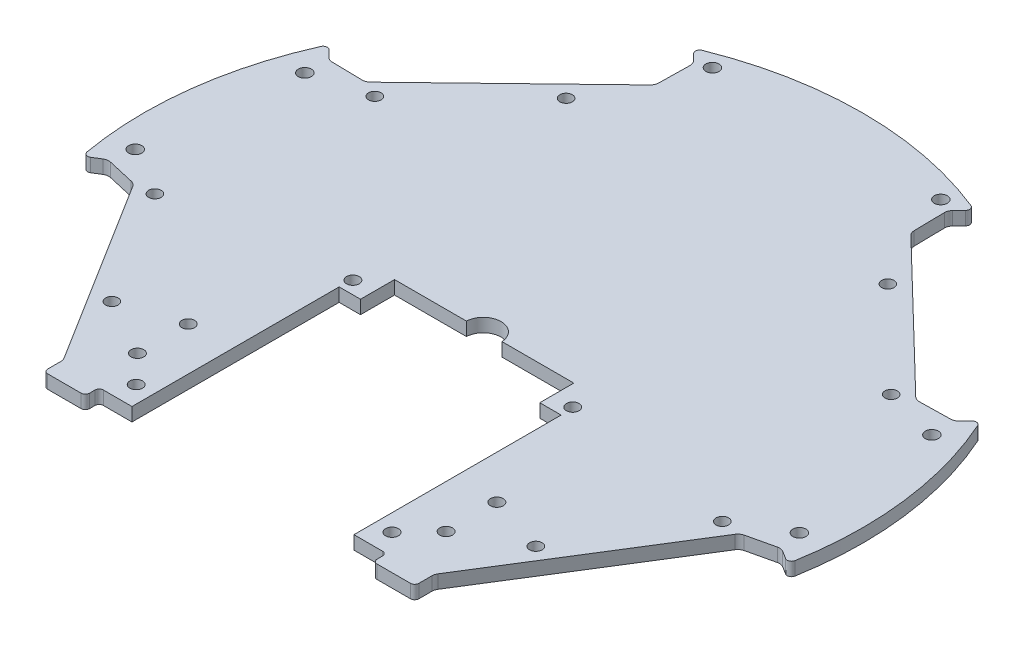
SolidWorks part; units mm, degrees
note: '?' marks a value the reader was unsure of.
material "6061 Alloy"
ref_plane "Front Plane" through (0, 0, 0) normal (0, 0, 1) x (1, 0, 0)
ref_plane "Top Plane" through (0, 0, 0) normal (0, 1, 0) x (1, 0, 0)
ref_plane "Right Plane" through (0, 0, 0) normal (1, 0, 0) x (0, 0, -1)
sketch "Sketch1" plane through (0, 0, 0) normal (0, 1, 0) x (1, 0, 0)
  line L0 (0, 0) -> (0, -62.55) construction
  line L1 (-83.4462, -16.178) -> (-71.2857, -8.5793) construction
  line L6 (0, 0) -> (-59.046, 61.1439) construction
  line L7 (0, 0) -> (-72.0841, -45.0431) construction
  line L8 (-33.174, 78.2591) -> (-23.2129, 67.9442) construction
  line L9 (-72.0841, -45.0431) -> (-70.388, -43.9833) construction
  line L10 (-70.388, -43.9833) -> (-84.9608, -20.662) construction
  line L11 (-84.9608, -20.662) -> (-72.2401, -12.7132) construction
  line L12 (-72.2401, -12.7132) -> (-43.0945, -59.3558) construction
  line L13 (-43.0945, -59.3558) -> (-55.8152, -67.3046) construction
  line L14 (-55.8152, -67.3046) -> (-70.388, -43.9833) construction
  line L21 (-59.046, 61.1439) -> (-57.6566, 59.7052)
  line L22 (-77.4385, 40.6021) -> (-37.8748, 78.8083) construction
  line L23 (-73.9694, 32.6911) -> (-77.0537, 35.885)
  line L24 (-37.8748, 78.8083) -> (-27.4549, 68.0182) construction
  line L25 (-27.4549, 68.0182) -> (-67.0186, 29.812) construction
  line L26 (-67.0186, 29.812) -> (-77.4385, 40.6021) construction
  line L27 (-43.0945, -64.8266) -> (-34, -64.8266)
  line L33 (-86.5505, -18.1178) -> (-71.2857, -8.5793) construction
  line L34 (0, 0) -> (0, 50000) construction
  line L35 (0, 0) -> (-50000, 0) construction
  line L36 (-57.5543, -62.55) -> (-19.8595, -62.55) construction
  line L38 (-67.0927, 25.57) -> (-79.5965, 38.5181) construction
  line L39 (-54.9774, -64.8266) -> (0, -64.8266) construction
  line L40 (-35.7168, 80.8923) -> (-23.2129, 67.9442) construction
  line L41 (-38.9606, -60.3102) -> (-54.2255, -69.8488) construction
  line L42 (-34, -62.55) -> (-19.8595, -62.55) construction
  line L43 (-43.0945, -64.8266) -> (-43.0945, -58.4123) construction
  line L45 (73.9694, 32.6911) -> (77.0537, 35.885)
  line L46 (-71.2857, -8.5793) -> (-38.9606, -60.3102) construction
  line L47 (83.4462, -16.178) -> (79.6809, -13.8252)
  line L48 (69.4846, -16.1792) -> (43.8945, -57.132)
  line L50 (43.0945, -64.8266) -> (34, -64.8266)
  line L51 (34, -62.55) -> (34, -64.8266)
  line L52 (0, 0) -> (72.0841, -45.0431) construction
  line L53 (0, 0) -> (59.046, 61.1439) construction
  line L54 (-30.0897, 75.0653) -> (-30.2847, 63.8954)
  line L55 (-62.7996, 32.4961) -> (-30.2847, 63.8954)
  line L56 (-30.0897, 75.0653) -> (-33.174, 78.2591)
  line L57 (73.9694, 32.6911) -> (77.0537, 35.885)
  line L58 (30.0897, 75.0653) -> (33.174, 78.2591)
  line L59 (-34, -62.55) -> (-34, -61.55)
  line L60 (62.7996, 32.4961) -> (30.2847, 63.8954)
  line L61 (-73.9694, 32.6911) -> (-62.7996, 32.4961)
  line L62 (-77.0537, 35.885) -> (-67.0927, 25.57) construction
  line L63 (-83.4462, -16.178) -> (-79.6809, -13.8252)
  line L64 (-79.6809, -13.8252) -> (-69.4846, -16.1792)
  line L65 (-69.4846, -16.1792) -> (-43.8945, -57.132)
  line L66 (-27.4549, 68.0182) -> (-23.2129, 67.9442) construction
  line L67 (-72.2401, -12.7132) -> (-71.2857, -8.5793) construction
  line L68 (30.0897, 75.0653) -> (30.2847, 63.8954)
  line L69 (73.9694, 32.6911) -> (62.7996, 32.4961)
  line L70 (-34, -62.55) -> (-34, -64.8266)
  line L71 (79.6809, -13.8252) -> (69.4846, -16.1792)
  line L72 (-34, -61.55) -> (-20, -61.55)
  line L73 (-20, -61.55) -> (-19.8595, -62.55)
  line L74 (-19.8595, -62.55) -> (19.8595, -62.55)
  line L75 (20, -61.55) -> (19.8595, -62.55)
  line L76 (34, -61.55) -> (20, -61.55)
  line L77 (34, -62.55) -> (34, -61.55)
  line L78 (-43.0945, -64.8266) -> (-43.8945, -64.8266)
  line L79 (-19.8595, -62.55) -> (0, -62.55) construction
  line L80 (-19.8595, -62.55) -> (34, -62.55) construction
  line L81 (-43.8945, -64.8266) -> (-43.8945, -57.132)
  line L82 (-43.0945, -58.4123) -> (-43.8945, -57.132) construction
  line L83 (43.8945, -64.8266) -> (43.8945, -57.132)
  line L84 (43.0945, -64.8266) -> (43.8945, -64.8266)
  line L97 (-23.2129, 67.9442) -> (-67.0927, 25.57) construction
  circle A0 centre (0, 0) radius 85 construction
  circle A1 centre (0, 0) radius 90 construction
  arc A51 (-77.0537, 35.885) -> (-83.4462, -16.178) centre (0, 0) ccw
  arc A52 (77.0537, 35.885) -> (83.4462, -16.178) centre (0, 0) cw
  arc A54 (-33.174, 78.2591) -> (33.174, 78.2591) centre (0, 0) cw
  point P29 (-31.6318, 76.6622)
  point P33 (-47.2368, 48.9151)
  point P34 (31.6318, 76.6622)
  point P35 (-57.6673, -36.0345)
  point P85 (-57.6566, 59.7052)
  dimension "D2" = 58
  dimension "D10" = 82
  dimension "D12" = 170
  dimension "D14" = 34
  dimension "D13" = 1
  dimension "D15" = 3
  dimension "D3" = 180
  dimension "D4" = 64.8266
  dimension "D5" = 44
  dimension "D6" = 15
  dimension "D7" = 55
  dimension "D8" = 62.55
  dimension "D9" = 2
  dimension "D11" = 2
  dimension "D16" = 7
  dimension "D17" = 7
  dimension "D18" = 0.5
  dimension "D19" = 1
  dimension "D20" = 14
  dimension "D21" = 0.8
extrude "Boss-Extrude4" add sketch "Sketch1" along normal mid plane 3.175
ref_point "Rear_Axle_Center (L)"
ref_axis "Rear_Axle_Proj (L)" through (46.5421, 0, -48.1958) along (0, 1, 0)?
ref_point "Front_Axle_Center (L)"
ref_axis "Front_Axle_Proj (L)" through (57.2432, 0, 35.7696) along (0, 1, 0)?
ref_point "Front_Axle_Center (R)"
ref_axis "Front_Axle_Proj (R)" through (-57.2432, 0, 35.7696) along (0, 1, 0)?
ref_point "Read_Axle_Center (R)"
ref_axis "Rear_Axle_Proj (R)" through (-46.5421, 0, -48.1958) along (0, 1, 0)?
sketch "Sketch17" plane through (0, 1.5875, 0) normal (0, 1, 0) x (1, 0, 0)
  line L0 (0, -57.55) -> (0, -62.55) construction
  line L1 (-19.8595, -62.55) -> (19.8595, -62.55) construction
  circle A0 centre (0, -57.55) radius 8.5
  dimension "D1" = 17
  dimension "D2" = 5
extrude "Boss-Extrude5" [suppressed] add sketch "Sketch17" against normal up to surface (3.175 mm away)
ref_plane "Plane1" through (0, 0, 10) normal (0, 0, 1) x (1, 0, 0)
hole_wizard "M3 Clearance Hole3" positions "Sketch18" profile "Sketch19" hole size "M3" standard "ANSI Metric" end condition through all
sketch "Sketch18" plane through (0, -1.5875, 0) normal (0, -1, 0) x (-1, 0, 0)
  line L0 (-36.5, -50) -> (-36.5, -38) construction
  line L3 (0, 0) -> (0, -38) construction
  line L4 (36.5, -50) -> (36.5, -38) construction
  line L6 (0, -38) -> (36.5, -38) construction
  line L8 (0, -38) -> (-36.5, -38) construction
  line L9 (-36.5, -44) -> (36.5, -44) construction
  line L10 (0, -44) -> (0, 0) construction
  point P1 (36.5, -50)
  point P3 (36.5, -38)
  point P5 (-36.5, -50)
  point P33 (-36.5, -38)
  dimension "D1" = 12
  dimension "D2" = 73
  dimension "D4" = 38
sketch "Sketch19" plane through (-36.5, -1.5875, 50) normal (1, 0, 0) x (0, 0, -1)
  line L0 (0, 0) -> (0, 3.175)
  line L1 (0, 3.175) -> (1.5, 3.175)
  line L2 (1.5, 3.175) -> (1.5, 0)
  line L5 (1.5, 0) -> (0, 0)
  line L11 (0, -6.35) -> (0, 107.95) construction
  dimension "Thru Hole Dia." = 3
  dimension "Thru Hole Depth" = 3.175
hole_wizard "M3 Clearance Hole1" positions "Sketch11" profile "Sketch12" hole size "M3" standard "ANSI Metric" end condition through all
sketch "Sketch11" plane through (0, 1.5875, 0) normal (0, 1, 0) x (1, 0, 0)
  line L0 (83.4462, -16.178) -> (79.6809, -13.8252) construction
  line L2 (73.9694, 32.6911) -> (77.0537, 35.885) construction
  line L4 (-73.9694, 32.6911) -> (-77.0537, 35.885) construction
  line L6 (0, 0) -> (0, -50000) construction
  line L7 (78.4111, 9.6277) -> (84.3664, 10.3589) construction
  line L10 (74.155, 27.2403) -> (78.5423, -8.4914) construction
  line L12 (78.4111, 9.6277) -> (76.3487, 9.3744) construction
  arc A7 (77.964, -12.7523) -> (72.563, 31.2347) centre (0, 0) ccw construction
  arc A13 (-77.964, -12.7523) -> (-72.563, 31.2347) centre (0, 0) cw construction
  arc A17 (83.4462, -16.178) -> (77.0537, 35.885) centre (0, 0) ccw construction
  point P34 (78.5423, -8.4914)
  point P66 (74.155, 27.2403)
  point P70 (-74.155, 27.2403)
  point P71 (-78.5423, -8.4914)
  dimension "D1" = 6
  dimension "D2" = 36
sketch "Sketch12" plane through (-78.5423, 1.5875, 8.4914) normal (1, 0, 0) x (0, 0, 1)
  line L0 (0, 0) -> (0, 3.175)
  line L1 (0, 3.175) -> (1.55, 3.175)
  line L2 (1.55, 3.175) -> (1.55, 0)
  line L5 (1.55, 0) -> (0, 0)
  line L11 (0, -6.35) -> (0, 107.95) construction
  dimension "Thru Hole Dia." = 3.1
  dimension "Thru Hole Depth" = 3.175
hole_wizard "M3 Clearance Hole4" positions "Sketch9" profile "Sketch10" hole size "M3" standard "ANSI Metric" end condition through all
sketch "Sketch9" plane through (0, -1.5875, 0) normal (0, -1, 0) x (-1, 0, 0)
  line L0 (0, 0) -> (0, 63.4318) construction
  line L1 (-38.0437, 52.9272) -> (38.0437, 52.9272) construction
  line L3 (61.0625, 30.6981) -> (-61.0625, 30.6981) construction
  line L4 (-67.0993, -15.2789) -> (67.0993, -15.2789) construction
  line L5 (50.1419, -42.4164) -> (-50.1419, -42.4164) construction
  line L6 (-61.0625, 30.6981) -> (-38.0437, 52.9272) construction
  line L7 (38.0437, 52.9272) -> (61.0625, 30.6981) construction
  line L8 (67.0993, -15.2789) -> (50.1419, -42.4164) construction
  line L9 (-50.1419, -42.4164) -> (-67.0993, -15.2789) construction
  line L10 (0, 0) -> (-44.8055, 46.3974) construction
  line L11 (0, 0) -> (44.8055, 46.3974) construction
  line L12 (0, 0) -> (-96.9468, 0) construction
  line L14 (-55.1231, -34.4448) -> (0, 0) construction
  line L15 (0, 0) -> (55.1231, -34.4448) construction
  line L18 (-69.4846, -16.1792) -> (-43.8945, -57.132) construction
  line L19 (-62.7996, 32.4961) -> (-30.2847, 63.8954) construction
  point P0 (-67.0993, -15.2789)
  point P2 (-50.1419, -42.4164)
  point P9 (-61.0625, 30.6981)
  point P11 (-38.0437, 52.9272)
  point P30 (50.1419, -42.4164)
  point P31 (67.0993, -15.2789)
  point P32 (38.0437, 52.9272)
  point P33 (61.0625, 30.6981)
  dimension "D9" = 46
  dimension "D10" = 46
  dimension "D11" = 32
  dimension "D12" = 32
  dimension "D7" = 58
  dimension "D5" = 32
  dimension "D6" = 2.5
  dimension "D8" = 9.4
  dimension "D2" = 44
  dimension "D3" = 32
  dimension "D4" = 2.5
  dimension "D13" = 9.4
sketch "Sketch10" plane through (67.0993, -1.5875, 15.2789) normal (1, 0, 0) x (0, 0, -1)
  line L0 (0, 0) -> (0, 3.175)
  line L1 (0, 3.175) -> (1.475, 3.175)
  line L2 (1.475, 3.175) -> (1.475, 0)
  line L5 (1.475, 0) -> (0, 0)
  line L11 (0, -6.35) -> (0, 107.95) construction
  dimension "Thru Hole Dia." = 2.95
  dimension "Thru Hole Depth" = 3.175
hole_wizard "M3 Clearance Hole2" positions "Sketch13" profile "Sketch14" hole size "M3" standard "ANSI Metric" end condition through all
sketch "Sketch13" plane through (0, 1.5875, 0) normal (0, 1, 0) x (1, 0, 0)
  line L0 (0, 0) -> (0, 85) construction
  line L2 (-24, 47) -> (-24, 81) construction
  line L3 (-24, 47) -> (24, 47) construction
  line L4 (-24, 81) -> (24, 81) construction
  line L5 (24, 47) -> (24, 81) construction
  line L6 (-24, 47) -> (24, 81) construction
  line L7 (-24, 81) -> (24, 47) construction
  line L8 (-38.0437, 52.9272) -> (-61.0625, 30.6981) construction
  line L10 (-36.307, 51.1289) -> (-59.3259, 28.8998) construction
  line L11 (-16.3488, 39.8187) -> (-31.6313, 55.6441) construction
  line L12 (-16.3488, 39.8187) -> (-48.7191, 8.559) construction
  line L13 (-31.6313, 55.6441) -> (-64.0016, 24.3845) construction
  line L14 (-48.7191, 8.559) -> (-64.0016, 24.3845) construction
  line L15 (-16.3488, 39.8187) -> (-64.0016, 24.3845) construction
  line L16 (-31.6313, 55.6441) -> (-48.7191, 8.559) construction
  line L17 (-49.5531, 41.8127) -> (-40.1752, 32.1016) construction
  line L18 (-27, 76.4978) -> (-27, 80.5978) construction
  arc A0 (33.174, 78.2591) -> (-33.174, 78.2591) centre (0, 0) ccw construction
  circle A1 centre (-16.2162, 44) radius 3 construction
  circle A2 centre (-27, 76.4978) radius 3 construction
  point P65 (0, 64)
  point P181 (-27, 76.4978)
  point P184 (27, 76.4978)
  dimension "D7" = 6
  dimension "D1" = 48
  dimension "D2" = 34
  dimension "D3" = 4
  dimension "D5" = 45
  dimension "D6" = 22
  dimension "D8" = 4.1
  dimension "D4" = 2.5
sketch "Sketch14" plane through (27, 1.5875, -76.4978) normal (1, 0, 0) x (0, 0, 1)
  line L0 (0, 0) -> (0, 3.175)
  line L1 (0, 3.175) -> (1.55, 3.175)
  line L2 (1.55, 3.175) -> (1.55, 0)
  line L5 (1.55, 0) -> (0, 0)
  line L11 (0, -6.35) -> (0, 107.95) construction
  dimension "Thru Hole Dia." = 3.1
  dimension "Thru Hole Depth" = 3.175
hole_wizard "M3 Clearance Hole5" [suppressed] positions "Sketch24" profile "Sketch25" hole size "M3" standard "ANSI Metric"
sketch "Sketch24" plane through (0, 1.5875, 0) normal (0, 1, 0) x (1, 0, 0)
  line L1 (-11, -4.4) -> (11, -4.4) construction
  line L2 (11, -4.4) -> (11, -36.4) construction
  line L3 (11, -36.4) -> (-11, -36.4) construction
  line L4 (-11, -36.4) -> (-11, -4.4) construction
  line L7 (-11, 37.6) -> (11, 37.6) construction
  line L8 (0, -4.4) -> (0, 0) construction
  line L9 (0, 0) -> (0, 37.6) construction
  point P8 (-11, -4.4)
  point P10 (11, -4.4)
  point P12 (11, -36.4)
  point P14 (-11, -36.4)
  point P42 (-11, 37.6)
  point P45 (11, 37.6)
  dimension "D1" = 22
  dimension "D2" = 32
  dimension "D3" = 4.4
  dimension "D4" = 42
sketch "Sketch25" plane through (-11, 1.5875, 4.4) normal (1, 0, 0) x (0, 0, 1)
  line L0 (0, 0) -> (0, 3.175)
  line L1 (0, 3.175) -> (1.5, 3.175)
  line L2 (1.5, 3.175) -> (1.5, 0)
  line L5 (1.5, 0) -> (0, 0)
  line L11 (0, -6.35) -> (0, 107.95) construction
  dimension "Thru Hole Dia." = 3
  dimension "Thru Hole Depth" = 3.175
sketch "Sketch20" plane through (0, 1.5875, 0) normal (0, 1, 0) x (1, 0, 0)
  line L0 (-16.1485, 44) -> (-16.1485, 39) construction
  line L1 (-14.6485, 44) -> (-14.6485, 39)
  line L2 (-17.6485, 44) -> (-17.6485, 39)
  line L3 (0, 0) -> (0, 85) construction
  line L5 (16.1485, 44) -> (16.1485, 39) construction
  line L6 (14.6485, 44) -> (14.6485, 39)
  line L7 (17.6485, 44) -> (17.6485, 39)
  arc A0 (-14.6485, 44) -> (-17.6485, 44) centre (-16.1485, 44) ccw
  arc A1 (-17.6485, 39) -> (-14.6485, 39) centre (-16.1485, 39) ccw
  arc A5 (33.174, 78.2591) -> (-33.174, 78.2591) centre (0, 0) ccw construction
  arc A7 (14.6485, 44) -> (17.6485, 44) centre (16.1485, 44) cw
  arc A8 (17.6485, 39) -> (14.6485, 39) centre (16.1485, 39) cw
  point P2 (-16.1485, 41.5)
  point P16 (16.1485, 41.5)
  dimension "D1" = 44
  dimension "D2" = 3
  dimension "D3" = 5
  dimension "D4" = 16.1485
extrude "Cut-Extrude1" [suppressed] cut sketch "Sketch20" against normal through all
sketch "Sketch22" plane through (0, 1.5875, 0) normal (0, 1, 0) x (1, 0, 0)
  line L0 (-56.6896, -36.6556) -> (-58.0464, -37.5035) construction
  line L1 (-69.4846, -16.1792) -> (-43.8945, -57.132) construction
  line L3 (30.2452, 66.1578) -> (65.062, 32.5356)
  line L4 (71.6894, -15.6702) -> (43.8945, -60.1514)
  line L5 (-19.8595, -62.55) -> (19.8595, -62.55) construction
  line L6 (-43.8945, -64.8266) -> (-43.8945, -57.132) construction
  line L28 (-30.2452, 66.1578) -> (-65.062, 32.5356)
  line L29 (-71.6894, -15.6702) -> (-43.8945, -60.1514)
  line L30 (-79.6809, -13.8252) -> (-69.4846, -16.1792) construction
  line L31 (0, 85) -> (0, -62.55) construction
  line L32 (-46.5421, 48.1958) -> (-47.6536, 49.3467) construction
  line L37 (-20, -61.55) -> (-19.8595, -62.55)
  line L38 (-20, -61.55) -> (-19.8595, -62.55)
  line L40 (-43.8945, -57.132) -> (-43.8945, -64.8266)
  line L41 (-43.8945, -57.132) -> (-43.8945, -64.8266)
  line L43 (43.8945, -64.8266) -> (43.8945, -57.132)
  line L44 (43.8945, -64.8266) -> (43.8945, -57.132)
  line L56 (-19.8595, -62.55) -> (19.8595, -62.55)
  line L58 (19.8595, -62.55) -> (20, -61.55)
  line L59 (20, -61.55) -> (34, -61.55)
  line L60 (34, -61.55) -> (34, -64.8266)
  line L61 (34, -64.8266) -> (43.8945, -64.8266)
  line L63 (43.8945, -57.132) -> (69.4846, -16.1792)
  line L64 (69.4846, -16.1792) -> (79.6809, -13.8252)
  line L65 (79.6809, -13.8252) -> (83.4462, -16.178)
  line L66 (77.0537, 35.885) -> (73.9694, 32.6911)
  line L67 (73.9694, 32.6911) -> (62.7996, 32.4961)
  line L68 (62.7996, 32.4961) -> (30.2847, 63.8954)
  line L69 (30.2847, 63.8954) -> (30.0897, 75.0653)
  line L70 (30.0897, 75.0653) -> (33.174, 78.2591)
  line L71 (-33.174, 78.2591) -> (-30.0897, 75.0653)
  line L72 (-30.0897, 75.0653) -> (-30.2847, 63.8954)
  line L73 (-30.2847, 63.8954) -> (-62.7996, 32.4961)
  line L74 (-62.7996, 32.4961) -> (-73.9694, 32.6911)
  line L75 (-73.9694, 32.6911) -> (-77.0537, 35.885)
  line L76 (-83.4462, -16.178) -> (-79.6809, -13.8252)
  line L77 (-79.6809, -13.8252) -> (-69.4846, -16.1792)
  line L78 (-69.4846, -16.1792) -> (-43.8945, -57.132)
  line L80 (-43.8945, -64.8266) -> (-34, -64.8266)
  line L81 (-34, -64.8266) -> (-34, -61.55)
  line L82 (-34, -61.55) -> (-20, -61.55)
  line L84 (-19.8595, -62.55) -> (19.8595, -62.55)
  line L86 (19.8595, -62.55) -> (20, -61.55)
  line L87 (20, -61.55) -> (34, -61.55)
  line L88 (34, -61.55) -> (34, -64.8266)
  line L89 (34, -64.8266) -> (43.8945, -64.8266)
  line L91 (43.8945, -57.132) -> (69.4846, -16.1792)
  line L92 (69.4846, -16.1792) -> (79.6809, -13.8252)
  line L93 (79.6809, -13.8252) -> (83.4462, -16.178)
  line L94 (77.0537, 35.885) -> (73.9694, 32.6911)
  line L95 (73.9694, 32.6911) -> (62.7996, 32.4961)
  line L96 (62.7996, 32.4961) -> (30.2847, 63.8954)
  line L97 (30.2847, 63.8954) -> (30.0897, 75.0653)
  line L98 (30.0897, 75.0653) -> (33.174, 78.2591)
  line L99 (-33.174, 78.2591) -> (-30.0897, 75.0653)
  line L100 (-30.0897, 75.0653) -> (-30.2847, 63.8954)
  line L101 (-30.2847, 63.8954) -> (-62.7996, 32.4961)
  line L102 (-62.7996, 32.4961) -> (-73.9694, 32.6911)
  line L103 (-73.9694, 32.6911) -> (-77.0537, 35.885)
  line L104 (-83.4462, -16.178) -> (-79.6809, -13.8252)
  line L105 (-79.6809, -13.8252) -> (-69.4846, -16.1792)
  line L106 (-69.4846, -16.1792) -> (-43.8945, -57.132)
  line L108 (-43.8945, -64.8266) -> (-34, -64.8266)
  line L109 (-34, -64.8266) -> (-34, -61.55)
  line L110 (-34, -61.55) -> (-20, -61.55)
  arc A9 (83.4462, -16.178) -> (77.0537, 35.885) centre (0, 0) ccw
  arc A10 (33.174, 78.2591) -> (-33.174, 78.2591) centre (0, 0) ccw
  arc A11 (-77.0537, 35.885) -> (-83.4462, -16.178) centre (0, 0) ccw
  arc A13 (83.4462, -16.178) -> (77.0537, 35.885) centre (0, 0) ccw
  arc A14 (33.174, 78.2591) -> (-33.174, 78.2591) centre (0, 0) ccw
  arc A15 (-77.0537, 35.885) -> (-83.4462, -16.178) centre (0, 0) ccw
  dimension "D2" = 1.6
  dimension "D1" = 0
extrude "Boss-Extrude6" add sketch "Sketch22" against normal up to surface (3.175 mm away) up to face at (-27, -1.5875, -74.9478)
fillet "Fillet1" radius 2 14 edges at (-30.0897, 0, -75.0653) (30.0897, 0, -75.0653) (-79.6809, 0, 13.8252) (79.6809, 0, 13.8252) (73.9694, 0, -32.6911) (-73.9694, 0, -32.6911) (65.062, 0, -32.5356) (30.2452, 0, -66.1578) (71.6894, 0, 15.6702) (-71.6894, 0, 15.6702) (-65.062, 0, -32.5356) (-30.2452, 0, -66.1578) (43.8945, 0, 60.1514) (-43.8945, 0, 60.1514)
fillet "Fillet3" radius 1 12 edges at (-77.0537, 0, -35.885) (77.0537, 0, -35.885) (83.4462, 0, 16.178) (34, 0, 64.8266) (-34, 0, 64.8266) (-33.174, 0, -78.2591) (33.174, 0, -78.2591) (-83.4462, 0, 16.178) (34, 0, 61.55) (-34, 0, 61.55) (-43.8945, 0, 64.8266) (43.8945, 0, 64.8266)
sketch "Sketch23" [suppressed] plane through (0, 3.175, 0) normal (0, 1, 0) x (1, 0, 0)
  circle A0 centre (0, -53.55) radius 4.95
  dimension "D1" = 9.9
fillet "Fillet6" radius 0.5 4 edges at (20, 0, 61.55) (19.8595, 0, 62.55) (-20, 0, 61.55) (-19.8595, 0, 62.55)
sketch "Sketch28" plane through (0, 1.5875, 0) normal (0, 1, 0) x (1, 0, 0)
  line L0 (-19.4248, -62.55) -> (19.4248, -62.55) construction
  line L1 (-19.4248, -62.55) -> (19.4248, -62.55) construction
  line L2 (-26.25, -62.55) -> (26.25, -62.55)
  line L3 (-26.25, -62.55) -> (-26.25, -12.55)
  line L4 (26.25, -62.55) -> (26.25, -12.55)
  line L5 (-26.25, -12.55) -> (26.25, -12.55)
  line L6 (0, -4.7) -> (0, -77.8833) construction
  line L7 (-21, -4.7) -> (-21, -12.55) construction
  line L8 (21, -4.7) -> (4, -4.7) construction
  line L9 (21, -4.7) -> (21, -12.55) construction
  line L10 (-4, -4.7) -> (-21, -4.7) construction
  line L11 (21.2, -4.5) -> (21.2, -12.55)
  line L12 (21.2, -4.5) -> (4.1952, -4.5)
  line L13 (-4.1952, -4.5) -> (-21.2, -4.5)
  line L14 (-21.2, -4.5) -> (-21.2, -12.55)
  arc A0 (19.4248, -62.55) -> (19.9199, -62.1196) centre (19.4248, -62.05) ccw construction
  arc A1 (4, -4.7) -> (-4, -4.7) centre (0, -4.7) ccw construction
  arc A2 (4.1952, -4.5) -> (-4.1952, -4.5) centre (0, -4.7) ccw
  point P11 (0, -62.55)
  point P16 (0, -12.55)
  point P23 (0, -4.7)
  dimension "D4" = 4
  dimension "D1" = 52.5
  dimension "D2" = 50
  dimension "D3" = 17
  dimension "D5" = 7.85
extrude "Cut-Extrude4" cut sketch "Sketch28" against normal blind 10 contours L8 A1 L10 L7 L5 L9 | L5 L3 L2 L4
extrude "Cut-Extrude2" [suppressed] cut sketch "Sketch23" against normal through all
sketch "Sketch26" [suppressed] plane through (0, 3.175, 0) normal (0, 1, 0) x (1, 0, 0)
  line L0 (0, 0) -> (0, 50) construction
  line L1 (-92.5, 5) -> (92.5, 5)
  line L2 (-92.5, 5) -> (-92.5, 95)
  line L3 (-92.5, 95) -> (92.5, 95)
  line L4 (92.5, 5) -> (92.5, 95)
  line L5 (-92.5, 5) -> (92.5, 95) construction
  line L6 (-92.5, 95) -> (92.5, 5) construction
  point P0 (0, 50)
  dimension "D1" = 90
  dimension "D2" = 185
  dimension "D3" = 5
extrude "Cut-Extrude3" [suppressed] cut sketch "Sketch26" against normal through all
fillet "Fillet4" [suppressed] radius 5
sketch "Sketch29" plane through (0, 1.5875, 0) normal (0, 1, 0) x (1, 0, 0)
  line L0 (-33, -61.55) -> (-26.25, -61.55) construction
  line L1 (0, -81.301) -> (0, 102.6168) construction
  line L2 (-26.25, -12.55) -> (-26.25, -61.55) construction
  line L3 (-26.25, -56.55) -> (-32.5626, -56.55) construction
  line L4 (-26.25, -56.55) -> (-30.25, -56.55)
  circle A0 centre (30.25, -56.55) radius 1.5
  circle A1 centre (-30.25, -56.55) radius 1.5
  dimension "D5" = 3
  dimension "D1" = 5
  dimension "D2" = 30.25
extrude "Cut-Extrude5" cut sketch "Sketch29" against normal blind 10
sketch "Sketch31" plane through (0, 1.5875, 0) normal (0, 1, 0) x (1, 0, 0)
  line L0 (26.25, -12.55) -> (21.2, -12.55) construction
  line L1 (0, 35.8655) -> (0, -81.8862) construction
  circle A0 centre (-26, -9.55) radius 1.5
  circle A1 centre (26, -9.55) radius 1.5
  dimension "D3" = 3
  dimension "D1" = 52
  dimension "D2" = 3
extrude "Cut-Extrude7" cut sketch "Sketch31" against normal blind 10
sketch "Sketch32" plane through (0, 1.5875, 0) normal (0, 1, 0) x (1, 0, 0)
  line L0 (-43.6016, -64.5337) -> (43.6016, -64.5337)
  line L1 (-43.6016, -64.5337) -> (-43.6016, 20.2064)
  line L2 (43.6016, -64.5337) -> (43.6016, 20.2064)
  line L3 (-43.6016, 20.2064) -> (43.6016, 20.2064)
  arc A0 (-43.8945, -63.8266) -> (-42.8945, -64.8266) centre (-42.8945, -63.8266) ccw construction
  arc A1 (42.8945, -64.8266) -> (43.8945, -63.8266) centre (42.8945, -63.8266) ccw construction
extrude "Cut-Extrude8" [suppressed] cut sketch "Sketch32" against normal blind 10 flip side to cut
sketch "Sketch33" [suppressed] plane through (0, -1.5875, 0) normal (0, -1, 0) x (1, 0, 0)
  line L0 (-43.6016, 64.5337) -> (-34.2929, 64.5337)
  line L1 (-43.6016, 64.5337) -> (-43.6016, 54.5337)
  line L2 (-34.2929, 64.5337) -> (-34.2929, 54.5337)
  line L3 (-43.6016, 54.5337) -> (-34.2929, 54.5337)
  line L4 (43.6016, 64.5337) -> (34.2929, 64.5337)
  line L5 (43.6016, 64.5337) -> (43.6016, 54.5337)
  line L6 (34.2929, 64.5337) -> (34.2929, 54.5337)
  line L7 (43.6016, 54.5337) -> (34.2929, 54.5337)
  line L9 (-43.6016, -20.2064) -> (-33.6016, -20.2064)
  line L10 (-43.6016, -20.2064) -> (-43.6016, -10.2064)
  line L11 (-43.6016, -10.2064) -> (-33.6016, -10.2064)
  line L12 (-33.6016, -20.2064) -> (-33.6016, -10.2064)
  line L13 (43.6016, -20.2064) -> (33.6016, -20.2064)
  line L14 (43.6016, -20.2064) -> (43.6016, -10.2064)
  line L15 (43.6016, -10.2064) -> (33.6016, -10.2064)
  line L16 (33.6016, -20.2064) -> (33.6016, -10.2064)
  dimension "D1" = 10
  dimension "D2" = 10
  dimension "D3" = 10
  dimension "D4" = 10
  dimension "D5" = 10
  dimension "D6" = 10
extrude "Boss-Extrude7" [suppressed] add sketch "Sketch33" along normal blind 5
equation "\"D3@Sketch9\"=\"D5@Sketch9\""
equation "\"D4@Sketch9\"=\"D6@Sketch9\""
equation "\"D13@Sketch9\"=\"D8@Sketch9\""
equation "\"D1@Sketch28\"=54.000000mm-1.5"
